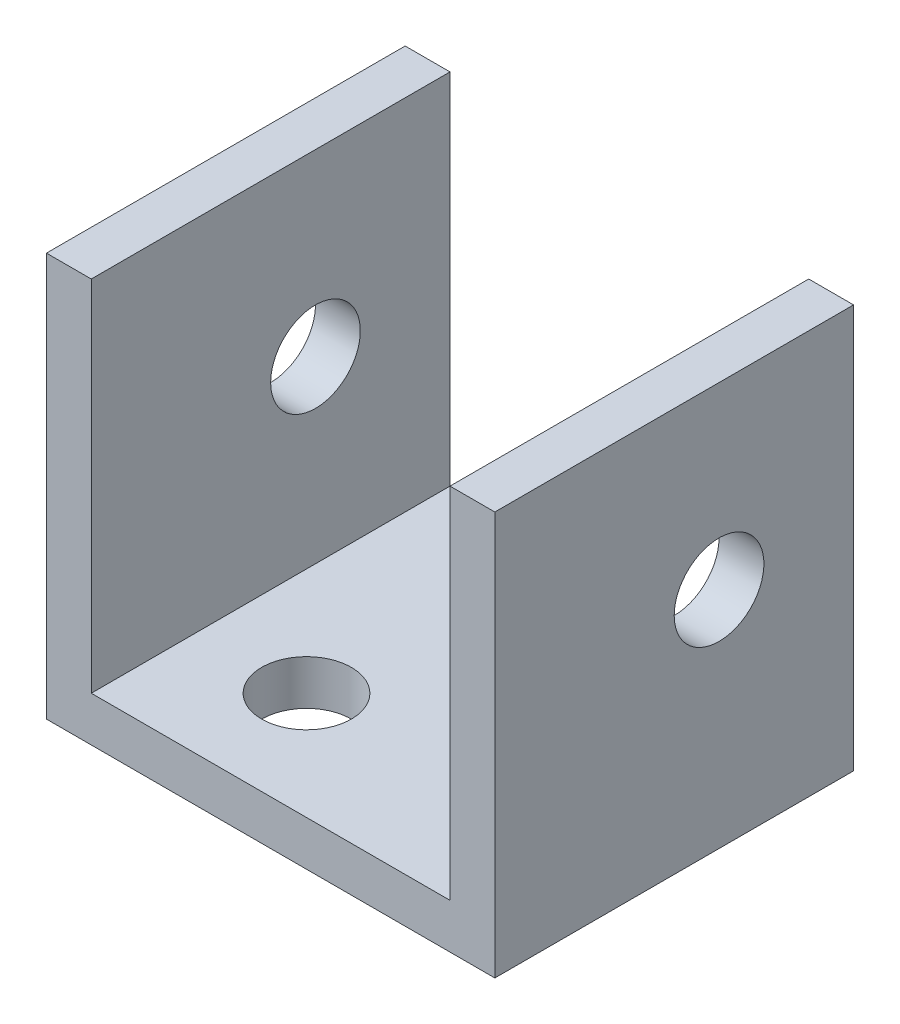
SolidWorks part; units mm, degrees
material "6061-T6 (SS)"
ref_plane "Front" through (0, 0, 0) normal (0, 0, 1) x (1, 0, 0)
ref_plane "Top" through (0, 0, 0) normal (0, 1, 0) x (1, 0, 0)
ref_plane "Right" through (0, 0, 0) normal (1, 0, 0) x (0, 0, -1)
sketch "Sketch1" plane through (0, 0, 0) normal (0, 1, 0) x (1, 0, 0)
  line L1 (-15.875, -12.7) -> (15.875, -12.7)
  line L2 (-15.875, -12.7) -> (-15.875, 12.7)
  line L3 (-15.875, 12.7) -> (15.875, 12.7)
  line L4 (15.875, -12.7) -> (15.875, 12.7)
  line L5 (-15.875, -12.7) -> (15.875, 12.7) construction
  line L6 (-15.875, 12.7) -> (15.875, -12.7) construction
  point P0 (0, 0)
  dimension "D1" = 31.75
  dimension "D2" = 25.4
extrude "Boss-Extrude1" add sketch "Sketch1" along normal blind 3.175
sketch "Sketch2" plane through (0, 3.175, 0) normal (0, 1, 0) x (1, 0, 0)
  line L0 (-15.875, 12.7) -> (-15.875, -12.7)
  line L1 (-15.875, -12.7) -> (-12.7, -12.7)
  line L2 (-15.875, -12.7) -> (15.875, -12.7) construction
  line L3 (-12.7, -12.7) -> (-12.7, 12.7)
  line L4 (15.875, 12.7) -> (-15.875, 12.7) construction
  line L5 (-12.7, 12.7) -> (-15.875, 12.7)
  line L6 (15.875, 12.7) -> (12.7, 12.7)
  line L7 (12.7, 12.7) -> (12.7, -12.7)
  line L8 (12.7, -12.7) -> (15.875, -12.7)
  line L9 (15.875, -12.7) -> (15.875, 12.7)
  dimension "D1" = 3.175
extrude "Boss-Extrude2" add sketch "Sketch2" along normal blind 25.4
sketch "Sketch6" plane through (0, 3.175, 0) normal (0, 1, 0) x (1, 0, 0)
  line L0 (12.7, 12.7) -> (-12.7, 12.7) construction
  line L1 (12.7, 12.7) -> (12.7, -12.7) construction
  line L2 (-12.7, -12.7) -> (-12.7, 12.7) construction
  line L3 (-12.7, -12.7) -> (12.7, -12.7) construction
  point P0 (5.08, 5.08)
  point P2 (-5.08, -5.08)
  dimension "D1" = 7.62
  dimension "D2" = 7.62
  dimension "D3" = 7.62
  dimension "D4" = 7.62
hole_wizard "1/4 (0.25) Diameter Hole1" positions "Sketch6" profile "Sketch5" hole size "1/4" standard "ANSI Inch" end condition through all
sketch "Sketch5" plane through (5.08, 3.175, -5.08) normal (1, 0, 0) x (0, 0, 1)
  line L0 (0, 0) -> (0, 3.175)
  line L1 (0, 3.175) -> (3.175, 3.175)
  line L2 (3.175, 3.175) -> (3.175, 0)
  line L5 (3.175, 0) -> (0, 0)
  line L11 (0, -6.35) -> (0, 107.95) construction
  dimension "Thru Hole Dia." = 6.35
  dimension "Thru Hole Depth" = 3.175
sketch "Sketch9" plane through (-15.875, 0, 0) normal (-1, 0, 0) x (0, 0, 1)
  line L0 (-12.7, 28.575) -> (12.7, 28.575) construction
  line L1 (-12.7, 28.575) -> (-12.7, 0) construction
  point P0 (-3.175, 15.875)
  dimension "D1" = 12.7
  dimension "D2" = 9.525
hole_wizard "1/4 (0.25) Diameter Hole2" positions "Sketch9" profile "Sketch8" hole size "1/4" standard "ANSI Inch" end condition through all
sketch "Sketch8" plane through (-15.875, 15.875, -3.175) normal (0, 1, 0) x (0, 0, 1)
  line L0 (0, 0) -> (0, 31.75)
  line L1 (0, 31.75) -> (3.175, 31.75)
  line L2 (3.175, 31.75) -> (3.175, 0)
  line L5 (3.175, 0) -> (0, 0)
  line L11 (0, -6.35) -> (0, 107.95) construction
  dimension "Thru Hole Dia." = 6.35
  dimension "Thru Hole Depth" = 31.75
